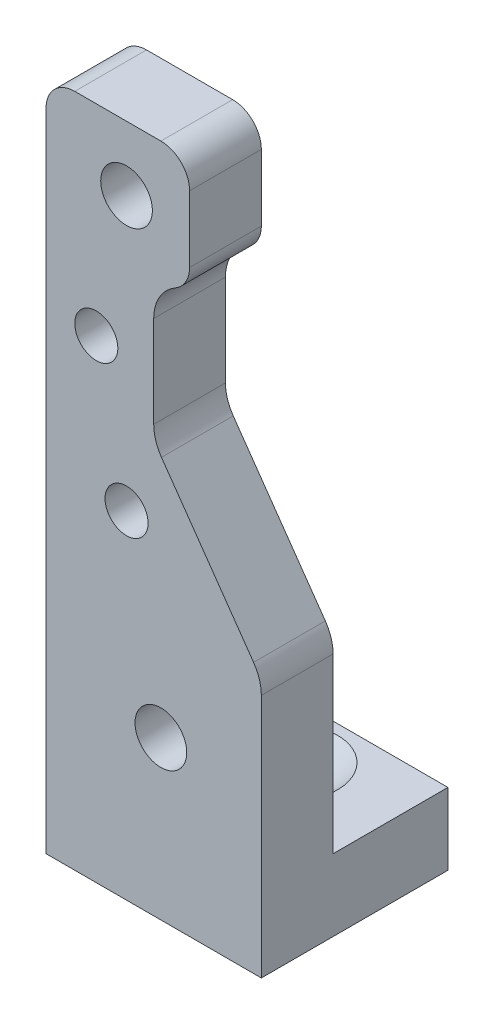
SolidWorks part; units mm, degrees
ref_plane "前视基准面" through (0, 0, 0) normal (0, 0, 1) x (1, 0, 0)
ref_plane "上视基准面" through (0, 0, 0) normal (0, 1, 0) x (1, 0, 0)
ref_plane "右视基准面" through (0, 0, 0) normal (1, 0, 0) x (0, 0, -1)
sketch "草图1" plane through (0, 0, 0) normal (1, 0, 0) x (0, 0, -1)
  line L0 (13, 5) -> (5, 5)
  line L1 (0, 0) -> (13, 0)
  line L2 (0, 0) -> (0, 18)
  line L3 (0, 18) -> (5, 18)
  line L4 (13, 0) -> (13, 5)
  line L5 (5, 5) -> (5, 18)
  dimension "D1" = 18
  dimension "D2" = 13
  dimension "D3" = 5
  dimension "D4" = 5
extrude "凸台-拉伸1" add sketch "草图1" along normal blind 10 and the other way blind 5
sketch "草图3" plane through (-10, 0, -5) normal (0, 0, -1) x (-1, 0, 0)
  line L2 (-5, 18) -> (-5, 47)
  line L3 (-5, 47) -> (-15, 47)
  line L5 (-15, 47) -> (-15, 39)
  line L6 (-15, 39) -> (-12.5, 39)
  line L8 (-12.5, 39) -> (-12.5, 28.7111)
  line L9 (-12.5, 28.7111) -> (-20, 18)
  line L12 (-5, 18) -> (-20, 18) construction
  line L13 (-20, 18) -> (-5, 18)
  dimension "D1" = 29
  dimension "D2" = 10
  dimension "D3" = 8
  dimension "D4" = 7.5
  dimension "D5" = 55
extrude "凸台-拉伸2" add sketch "草图3" against normal up to surface (5 mm away) up to face at (2.5, 9, 0)
sketch "草图2" plane through (-5, 0, 5) normal (-1, 0, 0) x (0, 0, 1)
  line L0 (-10, 15) -> (-18, 5)
  line L1 (-10, 5) -> (-10, 47) construction
  line L2 (-18, 5) -> (-10, 5) construction
  dimension "D1" = 8
  dimension "D2" = 10
rib "筋4" sketch "草图2" sketch "草图2" thickness 3 extrusion direction parallel to sketch draft on no parameters "D1"=3
hole_wizard "打孔尺寸(%根据十字)槽半沉头木螺钉的类型1" positions "草图4" profile "草图5" countersink size "M3" standard "GB" end condition through all
sketch "草图4" plane through (0, 0, -5) normal (0, 0, -1) x (-1, 0, 0)
  line L0 (-10, 5) -> (2, 5) construction
  line L1 (-10, 5) -> (-10, 18) construction
  line L2 (5, 47) -> (-5, 47) construction
  line L3 (5, 15) -> (5, 47) construction
  point P0 (-3, 11)
  point P16 (-0.6081, 42.5089)
  dimension "D1" = 6
  dimension "D2" = 7
  dimension "D3" = 4.4911
  dimension "D4" = 5.6081
sketch "草图5" plane through (3, 11, -5) normal (1, 0, 0) x (0, 1, 0)
  line L0 (0, 0) -> (0, 5)
  line L1 (0, 5) -> (1.8, 5)
  line L2 (1.8, 5) -> (1.8, 1.5)
  line L3 (1.8, 1.5) -> (3.3, 0)
  line L5 (3.3, 0) -> (0, 0)
  line L6 (-1.8, 1.5) -> (-3.3, 0) construction
  line L11 (0, -6.35) -> (0, 107.95) construction
  dimension "通孔孔直径" = 3.6
  dimension "通孔孔深度" = 5
  dimension "近端锥形沉头孔直径" = 6.6
  dimension "近端锥形沉头孔角度" = 90
hole_wizard "大小mm Transitional 暗销孔1" positions "草图6" profile "草图7" hole size "Ø3.0" standard "GB" end condition through all
sketch "草图6" plane through (0, 0, -5) normal (0, 0, -1) x (-1, 0, 0)
  point P0 (1.5, 33)
  point P3 (-0.6081, 23.4911)
sketch "草图7" plane through (-1.5, 33, -5) normal (1, 0, 0) x (0, 1, 0)
  line L0 (0, 0) -> (0, 5)
  line L1 (0, 5) -> (1.5, 5)
  line L2 (1.5, 5) -> (1.5, 0)
  line L5 (1.5, 0) -> (0, 0)
  line L11 (0, -6.35) -> (0, 107.95) construction
  dimension "通孔孔直径" = 3
  dimension "通孔孔深度" = 5
fillet "圆角1" radius 3 3 edges at (2.5, 28.7111, -2.5) (2.5, 39, -2.5) (10, 18, -2.5)
fillet "圆角2" radius 2 3 edges at (-5, 47, -2.5) (5, 47, -2.5) (5, 39, -2.5)
hole_wizard "打孔尺寸(%根据十字)槽半沉头木螺钉的类型2" positions "草图10" profile "草图11" countersink size "M3" standard "GB" end condition through all
sketch "草图10" plane through (0, 5, 0) normal (0, 1, 0) x (1, 0, 0)
  line L1 (-2, 13) -> (10, 13) construction
  line L2 (10, 13) -> (10, 5) construction
  point P0 (3, 9)
  point P5 (3, 9)
  point P11 (0, 0)
  point P12 (0, 0)
  point P13 (0, 0)
  point P14 (0, 0)
  point P15 (0, 0)
  dimension "D1" = 4
  dimension "D2" = 7
sketch "草图11" plane through (3, 5, -9) normal (1, 0, 0) x (0, 0, 1)
  line L0 (0, 0) -> (0, 5)
  line L1 (0, 5) -> (1.8, 5)
  line L2 (1.8, 5) -> (1.8, 1.5)
  line L3 (1.8, 1.5) -> (3.3, 0)
  line L5 (3.3, 0) -> (0, 0)
  line L6 (-1.8, 1.5) -> (-3.3, 0) construction
  line L11 (0, -6.35) -> (0, 107.95) construction
  dimension "通孔孔直径" = 3.6
  dimension "通孔孔深度" = 5
  dimension "近端锥形沉头孔直径" = 6.6
  dimension "近端锥形沉头孔角度" = 90
